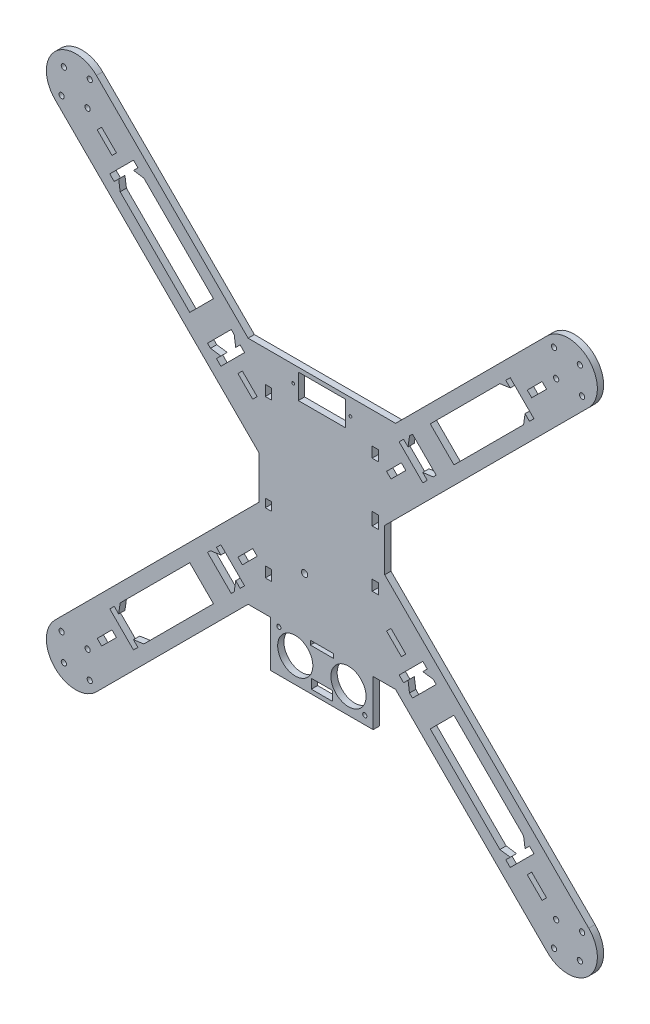
SolidWorks part; units mm, degrees
material "Custom Plastic"
ref_plane "Front Plane" through (0, 0, 0) normal (0, 0, 1) x (1, 0, 0)
ref_plane "Top Plane" through (0, 0, 0) normal (0, 1, 0) x (1, 0, 0)
ref_plane "Right Plane" through (0, 0, 0) normal (1, 0, 0) x (0, 0, -1)
sketch "Sketch1" plane through (0, 0, 0) normal (0, 0, 1) x (1, 0, 0)
  line L0 (117.5, 117.5) -> (-117.5, 117.5) construction
  line L1 (-117.5, 117.5) -> (117.5, -117.5) construction
  line L2 (117.5, -117.5) -> (-117.5, -117.5) construction
  line L3 (-117.5, -117.5) -> (117.5, 117.5) construction
  line L4 (117.5, 117.5) -> (117.5, -117.5) construction
  line L5 (-117.5, 117.5) -> (-117.5, -117.5) construction
  line L6 (0, 117.5) -> (0, -117.5) construction
  line L7 (35.201, 55) -> (-35.201, 55)
  line L8 (-30, 55) -> (30, 55) construction
  line L9 (-35.201, 55) -> (-107.6005, 127.3995)
  line L10 (-127.3995, 107.6005) -> (-30, 10.201)
  line L11 (-117.5, 0) -> (117.5, 0) construction
  line L12 (-30, 10.201) -> (-30, -10.201)
  line L13 (30, 55) -> (30, -55) construction
  line L14 (30, -55) -> (-30, -55) construction
  line L15 (-30, -55) -> (-30, 55) construction
  line L16 (30, 55) -> (-30, -55) construction
  line L17 (-24.5, -55) -> (-24.5, -77)
  line L18 (-127.3995, -107.6005) -> (-30, -10.201)
  line L19 (-24.5, -77) -> (24.5, -77)
  line L20 (-35.201, -55) -> (-107.6005, -127.3995)
  line L21 (35.201, -55) -> (24.5, -55)
  line L22 (35.201, -55) -> (107.6005, -127.3995)
  line L23 (127.3995, -107.6005) -> (30, -10.201)
  line L24 (30, 10.201) -> (30, -10.201)
  line L25 (127.3995, 107.6005) -> (30, 10.201)
  line L26 (35.201, 55) -> (107.6005, 127.3995)
  line L27 (24.5, -55) -> (24.5, -77)
  line L28 (-24.5, -55) -> (-35.201, -55)
  arc A0 (-107.6005, 127.3995) -> (-127.3995, 107.6005) centre (-117.5, 117.5) ccw
  arc A12 (-107.6005, -127.3995) -> (-127.3995, -107.6005) centre (-117.5, -117.5) cw
  arc A16 (107.6005, -127.3995) -> (127.3995, -107.6005) centre (117.5, -117.5) ccw
  arc A24 (107.6005, 127.3995) -> (127.3995, 107.6005) centre (117.5, 117.5) cw
  point P3 (0, 0)
  point P18 (0, 0)
  point P21 (0, -77)
  point P33 (-117.5, 117.5)
  point P34 (-30, 0)
  point P65 (0, -55)
  point P80 (0, 55)
  dimension "D3" = 14
  dimension "D8" = 24.5
  dimension "D7" = 22
  dimension "D1" = 235
  dimension "D2" = 235
  dimension "D4" = 60
  dimension "D5" = 110
  dimension "D6" = 28
extrude "Boss-Extrude1" add sketch "Sketch1" against normal blind 3
sketch "Sketch4" plane through (0, 0, 0) normal (0, 0, 1) x (1, 0, 0)
  line L0 (0, 0) -> (0, 55) construction
  line L1 (35.201, 55) -> (-35.201, 55) construction
  line L2 (0, 0) -> (-30, 0) construction
  line L3 (-30, 10.201) -> (-30, -10.201) construction
  line L4 (-30, 0) -> (-30, 10.201) construction
  line L5 (-30, 10.201) -> (-127.3995, 107.6005) construction
  line L6 (-35.201, 55) -> (-107.6005, 127.3995) construction
  line L7 (-107.6005, 127.3995) -> (-127.3995, 107.6005) construction
  line L8 (-110.7825, 124.2175) -> (-124.2175, 110.7825) construction
  line L9 (-123.1569, 123.1569) -> (-111.8431, 111.8431) construction
  circle A20 centre (-110.7825, 124.2175) radius 1.25
  circle A21 centre (-124.2175, 110.7825) radius 1.25
  circle A22 centre (-123.1569, 123.1569) radius 1.25
  circle A23 centre (-111.8431, 111.8431) radius 1.25
  circle A24 centre (111.8431, 111.8431) radius 1.25
  circle A25 centre (110.7825, 124.2175) radius 1.25
  circle A26 centre (123.1569, 123.1569) radius 1.25
  circle A27 centre (124.2175, 110.7825) radius 1.25
  circle A28 centre (111.8431, -111.8431) radius 1.25
  circle A29 centre (124.2175, -110.7825) radius 1.25
  circle A30 centre (123.1569, -123.1569) radius 1.25
  circle A31 centre (110.7825, -124.2175) radius 1.25
  circle A32 centre (-111.8431, -111.8431) radius 1.25
  circle A33 centre (-110.7825, -124.2175) radius 1.25
  circle A34 centre (-123.1569, -123.1569) radius 1.25
  circle A35 centre (-124.2175, -110.7825) radius 1.25
  point P16 (-117.5, 117.5)
  point P19 (-117.5, 117.5)
  point P26 (-117.5, 117.5)
  point P62 (0, 0)
  dimension "D4" = 2.5
  dimension "D2" = 19
  dimension "D3" = 16
extrude "Cut-Extrude1" cut sketch "Sketch4" against normal blind 3
sketch "Sketch5" plane through (0, 0, 0) normal (0, 0, 1) x (1, 0, 0)
  line L7 (-11.25, 53) -> (-11.25, 41.2)
  line L8 (-11.25, 41.2) -> (11.25, 41.2)
  line L9 (11.25, 41.2) -> (11.25, 53)
  line L10 (11.25, 53) -> (-11.25, 53)
  line L12 (0, 53) -> (0, 41.2) construction
  line L13 (-13.65, 47.1) -> (13.65, 47.1) construction
  line L14 (35.201, 55) -> (-35.201, 55) construction
  circle A2 centre (-13.65, 47.1) radius 0.65
  circle A3 centre (13.65, 47.1) radius 0.65
  point P20 (0, 47.1)
  point P21 (0, 47.1)
  point P26 (0, 55)
  dimension "D8" = 1.3
  dimension "D9" = 1.3
  dimension "D10" = 27.3
  dimension "D11" = 22.5
  dimension "D12" = 11.8
  dimension "D13" = 2
extrude "Cut-Extrude2" cut sketch "Sketch5" against normal blind 3
sketch "Sketch6" plane through (0, 0, 0) normal (0, 0, 1) x (1, 0, 0)
  line L1 (-11.25, 41.2) -> (11.25, 41.2) construction
  circle A0 centre (-8.25, -28.8) radius 1.5
  dimension "D3" = 3
  dimension "D1" = 70
  dimension "D2" = 3
extrude "Cut-Extrude3" cut sketch "Sketch6" against normal blind 3
sketch "Sketch7" plane through (0, 0, 0) normal (0, 0, 1) x (1, 0, 0)
  line L0 (-22.5, -55) -> (-22.5, -75) construction
  line L5 (-22.5, -75) -> (22.5, -75) construction
  line L6 (22.5, -75) -> (22.5, -55) construction
  line L7 (22.5, -55) -> (-22.5, -55) construction
  line L8 (0, -55) -> (0, -75) construction
  line L9 (-12.7, -65) -> (0, -65) construction
  line L10 (-24.5, -77) -> (24.5, -77) construction
  line L11 (-24.5, -55) -> (-24.5, -77) construction
  line L12 (-5.5, -55) -> (-5.5, -57)
  line L13 (-5.5, -57) -> (5.5, -57)
  line L15 (5.5, -55) -> (-5.5, -55)
  line L16 (-5, -75) -> (-5, -70.5)
  line L17 (-5, -70.5) -> (5, -70.5)
  line L21 (5, -75) -> (-5, -75)
  line L22 (5.5, -55) -> (5.5, -57)
  line L23 (5, -75) -> (5, -70.5)
  circle A5 centre (-20.5, -57) radius 1
  circle A6 centre (-12.7, -65) radius 8.4
  circle A7 centre (12.7, -65) radius 8.4
  circle A8 centre (20.5, -73) radius 1
  point P25 (0, -57)
  point P26 (0, -70.5)
  dimension "D3" = 2
  dimension "D6" = 20
  dimension "D13" = 5
  dimension "D5" = 45
  dimension "D1" = 2
  dimension "D4" = 16.8
  dimension "D14" = 2
  dimension "D2" = 2
  dimension "D7" = 2
  dimension "D8" = 2
  dimension "D9" = 12.7
  dimension "D10" = 5.5
  dimension "D11" = 2
  dimension "D12" = 4.5
  dimension "D15" = 2
  dimension "D16" = 2
extrude "Cut-Extrude4" cut sketch "Sketch7" against normal blind 3
sketch "Sketch8" plane through (0, 0, 0) normal (0, 0, 1) x (1, 0, 0)
  line L0 (101.2365, -89.9228) -> (89.9228, -101.2365)
  line L1 (89.9228, -101.2365) -> (87.8015, -99.1152)
  line L2 (36.8898, -48.2035) -> (48.2035, -36.8898)
  line L3 (48.2035, -36.8898) -> (50.3249, -39.0111)
  line L4 (105.4792, -85.6802) -> (85.6802, -105.4792) construction
  line L5 (127.3995, -107.6005) -> (30, -10.201) construction
  line L6 (35.201, -55) -> (107.6005, -127.3995) construction
  line L7 (40.0718, -37.9505) -> (37.9505, -40.0718)
  line L8 (115.8431, -107.8431) -> (111.8431, -111.8431) construction
  line L9 (37.9505, -40.0718) -> (30.8794, -33.0007)
  line L10 (50.3249, 39.0111) -> (48.2035, 36.8898)
  line L11 (30.8794, -33.0007) -> (33.0007, -30.8794)
  line L12 (33.0007, -30.8794) -> (40.0718, -37.9505)
  line L13 (42.5467, -42.5467) -> (39.0111, -39.0111) construction
  line L14 (35.201, -55) -> (107.6005, -127.3995) construction
  line L15 (100.1759, -98.0546) -> (98.0546, -100.1759)
  line L16 (98.0546, -100.1759) -> (105.1256, -107.247)
  line L17 (105.1256, -107.247) -> (107.247, -105.1256)
  line L18 (107.247, -105.1256) -> (100.1759, -98.0546)
  line L19 (99.1152, -99.1152) -> (95.5797, -95.5797) construction
  line L20 (-101.2365, -89.9228) -> (-99.1152, -87.8015)
  line L21 (-100.1759, -98.0546) -> (-107.247, -105.1256)
  line L22 (-107.247, -105.1256) -> (-105.1256, -107.247)
  line L23 (-105.1256, -107.247) -> (-98.0546, -100.1759)
  line L24 (-98.0546, -100.1759) -> (-100.1759, -98.0546)
  line L25 (-89.9228, -101.2365) -> (-101.2365, -89.9228)
  line L26 (-36.8898, -48.2035) -> (-39.0111, -50.3249)
  line L27 (-48.2035, -36.8898) -> (-36.8898, -48.2035)
  line L28 (-37.9505, -40.0718) -> (-40.0718, -37.9505)
  line L29 (-30.8794, -33.0007) -> (-37.9505, -40.0718)
  line L30 (-40.0718, -37.9505) -> (-33.0007, -30.8794)
  line L31 (-33.0007, -30.8794) -> (-30.8794, -33.0007)
  line L32 (-89.9228, 101.2365) -> (-87.8015, 99.1152)
  line L33 (-98.0546, 100.1759) -> (-105.1256, 107.247)
  line L34 (-105.1256, 107.247) -> (-107.247, 105.1256)
  line L35 (-107.247, 105.1256) -> (-100.1759, 98.0546)
  line L36 (-100.1759, 98.0546) -> (-98.0546, 100.1759)
  line L37 (-101.2365, 89.9228) -> (-89.9228, 101.2365)
  line L38 (-48.2035, 36.8898) -> (-50.3249, 39.0111)
  line L39 (-36.8898, 48.2035) -> (-48.2035, 36.8898)
  line L40 (-40.0718, 37.9505) -> (-37.9505, 40.0718)
  line L41 (-33.0007, 30.8794) -> (-40.0718, 37.9505)
  line L42 (-37.9505, 40.0718) -> (-30.8794, 33.0007)
  line L43 (-30.8794, 33.0007) -> (-33.0007, 30.8794)
  line L44 (101.2365, 89.9228) -> (99.1152, 87.8015)
  line L45 (100.1759, 98.0546) -> (107.247, 105.1256)
  line L46 (107.247, 105.1256) -> (105.1256, 107.247)
  line L47 (105.1256, 107.247) -> (98.0546, 100.1759)
  line L48 (98.0546, 100.1759) -> (100.1759, 98.0546)
  line L49 (89.9228, 101.2365) -> (101.2365, 89.9228)
  line L50 (36.8898, 48.2035) -> (39.0111, 50.3249)
  line L51 (48.2035, 36.8898) -> (36.8898, 48.2035)
  line L52 (37.9505, 40.0718) -> (40.0718, 37.9505)
  line L53 (30.8794, 33.0007) -> (37.9505, 40.0718)
  line L54 (40.0718, 37.9505) -> (33.0007, 30.8794)
  line L55 (33.0007, 30.8794) -> (30.8794, 33.0007)
  line L56 (30, 10.201) -> (127.3995, 107.6005) construction
  line L57 (41.8396, 53.1533) -> (84.9731, 96.2868)
  line L58 (96.2868, 84.9731) -> (53.1533, 41.8396)
  line L59 (87.8015, 99.1152) -> (89.9228, 101.2365)
  line L60 (99.1152, -87.8015) -> (96.9939, -89.9228)
  line L61 (-96.2868, -84.9731) -> (-53.1533, -41.8396)
  line L62 (96.9939, -89.9228) -> (96.2868, -84.9731)
  line L63 (99.1152, -87.8015) -> (101.2365, -89.9228)
  line L64 (87.8015, -99.1152) -> (89.9228, -96.9939)
  line L65 (-87.8015, -99.1152) -> (-89.9228, -101.2365)
  line L66 (89.9228, -96.9939) -> (84.9731, -96.2868)
  line L67 (84.9731, -96.2868) -> (41.8396, -53.1533)
  line L68 (50.3249, -39.0111) -> (48.2035, -41.1325)
  line L69 (48.2035, -41.1325) -> (53.1533, -41.8396)
  line L70 (53.1533, -41.8396) -> (96.2868, -84.9731)
  line L71 (39.0111, -50.3249) -> (41.1325, -48.2035)
  line L72 (41.1325, -48.2035) -> (41.8396, -53.1533)
  line L73 (39.0111, -50.3249) -> (36.8898, -48.2035)
  line L74 (-89.9228, -96.9939) -> (-84.9731, -96.2868)
  line L75 (-87.8015, -99.1152) -> (-89.9228, -96.9939)
  line L76 (-96.9939, -89.9228) -> (-96.2868, -84.9731)
  line L77 (-99.1152, -87.8015) -> (-96.9939, -89.9228)
  line L78 (-41.1325, -48.2035) -> (-41.8396, -53.1533)
  line L79 (-39.0111, -50.3249) -> (-41.1325, -48.2035)
  line L80 (-48.2035, -41.1325) -> (-53.1533, -41.8396)
  line L81 (-50.3249, -39.0111) -> (-48.2035, -41.1325)
  line L82 (-96.9939, 89.9228) -> (-96.2868, 84.9731)
  line L83 (-99.1152, 87.8015) -> (-96.9939, 89.9228)
  line L84 (-89.9228, 96.9939) -> (-84.9731, 96.2868)
  line L85 (-87.8015, 99.1152) -> (-89.9228, 96.9939)
  line L86 (-48.2035, 41.1325) -> (-53.1533, 41.8396)
  line L87 (-50.3249, 39.0111) -> (-48.2035, 41.1325)
  line L88 (-41.1325, 48.2035) -> (-41.8396, 53.1533)
  line L89 (-39.0111, 50.3249) -> (-41.1325, 48.2035)
  line L90 (89.9228, 96.9939) -> (84.9731, 96.2868)
  line L91 (87.8015, 99.1152) -> (89.9228, 96.9939)
  line L92 (96.9939, 89.9228) -> (96.2868, 84.9731)
  line L93 (99.1152, 87.8015) -> (96.9939, 89.9228)
  line L94 (41.1325, 48.2035) -> (41.8396, 53.1533)
  line L95 (39.0111, 50.3249) -> (41.1325, 48.2035)
  line L96 (48.1429, 41.1931) -> (53.1533, 41.8396)
  line L97 (50.3249, 39.0111) -> (48.1429, 41.1931)
  line L98 (-39.0111, 50.3249) -> (-36.8898, 48.2035)
  line L99 (-53.1533, 41.8396) -> (-96.2868, 84.9731)
  line L100 (-99.1152, 87.8015) -> (-101.2365, 89.9228)
  line L101 (-84.9731, 96.2868) -> (-41.8396, 53.1533)
  line L102 (-41.8396, -53.1533) -> (-84.9731, -96.2868)
  line L103 (-50.3249, -39.0111) -> (-48.2035, -36.8898)
  line L104 (96.2868, 84.9731) -> (84.9731, 96.2868) construction
  line L105 (53.1533, 41.8396) -> (41.8396, 53.1533) construction
  point P10 (95.5797, -95.5797)
  point P11 (95.5797, -95.5797)
  point P18 (-49.2642, 40.0718)
  point P19 (-49.2642, -40.0718)
  point P68 (0, 0)
  point P122 (0, 0)
  dimension "D1" = 23
  dimension "D2" = 75
  dimension "D3" = 3
  dimension "D4" = 10
  dimension "D5" = 5
  dimension "D6" = 6
  dimension "D7" = 3
  dimension "D8" = 10
  dimension "D9" = 5
  dimension "D11" = 6
  dimension "D12" = 3
  dimension "D13" = 4
  dimension "D14" = 3
  dimension "D15" = 3
  dimension "D16" = 4
  dimension "D17" = 3
  dimension "D18" = 3
  dimension "D19" = 4
  dimension "D20" = 3
  dimension "D21" = 3
  dimension "D22" = 4
  dimension "D23" = 3
  dimension "D24" = 3
  dimension "D25" = 4
  dimension "D26" = 3
  dimension "D27" = 4
  dimension "D28" = 3
  dimension "D29" = 3
  dimension "D30" = 4
  dimension "D31" = 4
  dimension "D32" = 3
  dimension "D33" = 3
  dimension "D34" = 4
  dimension "D35" = 4
  dimension "D36" = 3
  dimension "D37" = 3
  dimension "D38" = 4
  dimension "D39" = 4
  dimension "D40" = 3
  dimension "D41" = 3
  dimension "D42" = 4
  dimension "D43" = 4
  dimension "D10" = 4
extrude "Cut-Extrude5" cut sketch "Sketch8" against normal through all
sketch "Sketch9" plane through (-5.6569, 5.6569, 0) normal (0.7071, -0.7071, 0) x (0, 0, -1)
  line L0 (3, 128.1701) -> (3, 67.1701) construction
  line L1 (3, 81.1701) -> (0, 81.1701)
  line L2 (3, 81.1701) -> (3, 69.1701)
  line L3 (3, 69.1701) -> (0, 69.1701)
  line L4 (0, 81.1701) -> (0, 69.1701)
  line L5 (0, 128.1701) -> (0, 67.1701) construction
  line L6 (0, 0) -> (28.0274, 0) construction
  line L7 (3, 63.1701) -> (0, 63.1701) construction
  dimension "D1" = 6
  dimension "D2" = 12
extrude "Boss-Extrude2" add sketch "Sketch9" along normal up to next
sketch "Sketch11" plane through (5.6569, 5.6569, 0) normal (-0.7071, -0.7071, 0) x (0, 0, 1)
  line L0 (-3, -128.1701) -> (-3, -67.1701) construction
  line L1 (-3, -69.1701) -> (0, -69.1701)
  line L2 (-3, -69.1701) -> (-3, -81.1701)
  line L3 (-3, -81.1701) -> (0, -81.1701)
  line L4 (0, -69.1701) -> (0, -81.1701)
  line L5 (0, -128.1701) -> (0, -67.1701) construction
  line L6 (-3, -63.1701) -> (0, -63.1701) construction
  dimension "D1" = 6
  dimension "D2" = 12
extrude "Boss-Extrude3" add sketch "Sketch11" along normal up to next
sketch "Sketch12" plane through (5.6569, -5.6569, 0) normal (-0.7071, 0.7071, 0) x (0, 0, 1)
  line L0 (-3, -128.1701) -> (-3, -67.1701) construction
  line L1 (-3, -69.1701) -> (0, -69.1701)
  line L2 (-3, -69.1701) -> (-3, -81.1701)
  line L3 (-3, -81.1701) -> (0, -81.1701)
  line L4 (0, -69.1701) -> (0, -81.1701)
  line L5 (0, -128.1701) -> (0, -67.1701) construction
  dimension "D1" = 6
  dimension "D2" = 12
extrude "Boss-Extrude4" add sketch "Sketch12" along normal up to next
sketch "Sketch13" plane through (5.6569, 5.6569, 0) normal (-0.7071, -0.7071, 0) x (0, 0, 1)
  line L0 (-3, 67.1701) -> (-3, 128.1701) construction
  line L1 (-3, 69.1701) -> (0, 69.1701)
  line L2 (-3, 69.1701) -> (-3, 81.1701)
  line L3 (-3, 81.1701) -> (0, 81.1701)
  line L4 (0, 69.1701) -> (0, 81.1701)
  line L5 (0, 67.1701) -> (0, 128.1701) construction
  dimension "D1" = 6
  dimension "D2" = 12
extrude "Boss-Extrude5" add sketch "Sketch13" along normal up to next
sketch "Sketch14" plane through (0, 0, -3) normal (0, 0, -1) x (-1, 0, 0)
  line L0 (30, 0) -> (-30, 0) construction
  line L1 (30, 10.201) -> (30, -10.201) construction
  line L2 (-30, -10.201) -> (-30, 10.201) construction
  line L3 (25.5, -40) -> (25.5, 40) construction
  line L12 (24, -35) -> (-25.5, -35) construction
  line L13 (-25.5, -35) -> (-25.5, -15) construction
  line L14 (-24, 13) -> (-24, 7)
  line L17 (-24, 7) -> (-27, 7)
  line L19 (-24, 13) -> (-27, 13)
  line L23 (24, -40) -> (27, -40)
  line L24 (24, -40) -> (24, -35)
  line L25 (24, -35) -> (27, -35)
  line L26 (27, -40) -> (27, -35)
  line L27 (24, -11) -> (27, -11)
  line L28 (24, -11) -> (24, -7)
  line L29 (24, -7) -> (27, -7)
  line L30 (27, -11) -> (27, -7)
  line L31 (24, 35) -> (27, 35)
  line L32 (24, 35) -> (24, 40)
  line L33 (24, 40) -> (27, 40)
  line L34 (27, 35) -> (27, 40)
  line L35 (-27, 13) -> (-27, 7)
  line L37 (-24, -20) -> (-27, -20)
  line L38 (-24, -20) -> (-24, -15)
  line L39 (-24, -15) -> (-27, -15)
  line L40 (-27, -20) -> (-27, -15)
  line L41 (-24, 35) -> (-27, 35)
  line L42 (-24, 35) -> (-24, 40)
  line L43 (-24, 40) -> (-27, 40)
  line L44 (-27, 35) -> (-27, 40)
  point P11 (25.5, -40)
  point P16 (25.5, 0)
  point P28 (-25.5, 13)
  point P38 (-25.5, 7)
  dimension "D1" = 80
  dimension "D2" = 3
  dimension "D3" = 5
  dimension "D4" = 24
  dimension "D5" = 20
  dimension "D6" = 22
  dimension "D7" = 6
  dimension "D8" = 5
  dimension "D9" = 22
  dimension "D10" = 4
  dimension "D11" = 5
  dimension "D12" = 42
  dimension "D13" = 5
extrude "Cut-Extrude6" cut sketch "Sketch14" against normal through all
